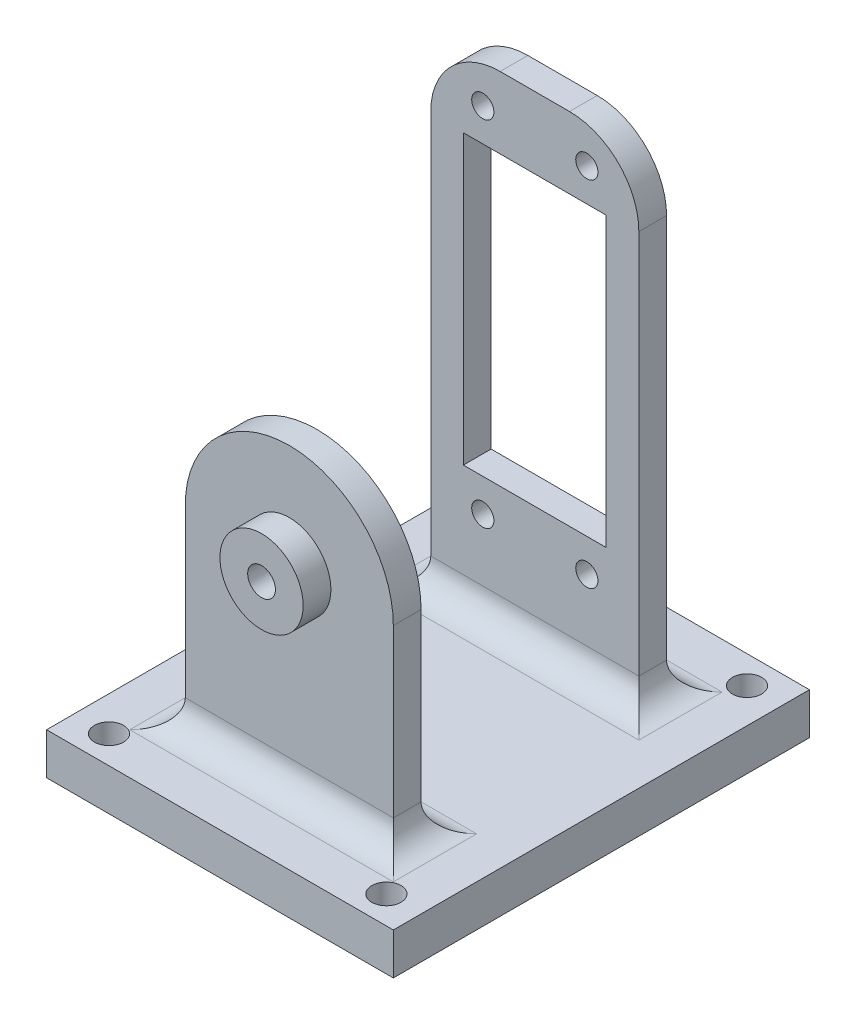
SolidWorks part; units mm, degrees
ref_plane "Front Plane" through (0, 0, 0) normal (0, 0, 1) x (1, 0, 0)
ref_plane "Top Plane" through (0, 0, 0) normal (0, 1, 0) x (1, 0, 0)
ref_plane "Right Plane" through (0, 0, 0) normal (1, 0, 0) x (0, 0, -1)
sketch "Sketch1" plane through (0, 0, 0) normal (0, 0, 1) x (1, 0, 0)
  line L0 (0, 0) -> (0, 53.2406) construction
  line L5 (-15, -28) -> (15, -28)
  line L6 (-15, -28) -> (-15, 31.5)
  line L7 (-5, 41.5) -> (5, 41.5)
  line L8 (15, -28) -> (15, 31.5)
  line L10 (-10.3, -10.3) -> (10.3, -10.3)
  line L11 (-10.3, -10.3) -> (-10.3, 31.2)
  line L12 (-10.3, 31.2) -> (10.3, 31.2)
  line L13 (10.3, -10.3) -> (10.3, 31.2)
  arc A0 (5, 41.5) -> (15, 31.5) centre (5, 31.5) cw
  arc A1 (-15, 31.5) -> (-5, 41.5) centre (-5, 31.5) cw
  circle A2 centre (-7.5, 35.95) radius 1.6
  circle A3 centre (-7.5, -15.05) radius 1.6
  circle A4 centre (7.5, 35.95) radius 1.6
  circle A5 centre (7.5, -15.05) radius 1.6
  dimension "D4" = 10
  dimension "D10" = 3.2
  dimension "D13" = 3.2
  dimension "D1" = 30
  dimension "D2" = 41.5
  dimension "D3" = 28
  dimension "D5" = 20.6
  dimension "D6" = 31.2
  dimension "D7" = 10.3
  dimension "D8" = 7.5
  dimension "D9" = 35.95
  dimension "D11" = 7.5
  dimension "D12" = 15.05
extrude "Boss-Extrude1" add sketch "Sketch1" along normal blind 4
ref_plane "Plane1" through (0, 0, 39.4) normal (0, 0, 1) x (1, 0, 0)
sketch "Sketch2" plane through (0, 0, 39.4) normal (0, 0, 1) x (1, 0, 0)
  line L0 (0, 0) -> (0, 30.7043) construction
  line L1 (-15, -28) -> (15, -28)
  line L2 (-15, -28) -> (-15, 0)
  line L4 (15, -28) -> (15, 0)
  arc A0 (-15, 0) -> (15, 0) centre (0, 0) cw
  point P8 (0, 0)
  dimension "D3" = 15
  dimension "D1" = 30
  dimension "D2" = 28
extrude "Boss-Extrude2" add sketch "Sketch2" against normal blind 4 separate body
sketch "Sketch3" plane through (0, 0, 39.4) normal (0, 0, 1) x (1, 0, 0)
  circle A0 centre (0, 0) radius 6
  dimension "D1" = 12
extrude "Boss-Extrude3" add sketch "Sketch3" along normal blind 4
sketch "Sketch4" plane through (0, 0, 43.4) normal (0, 0, 1) x (1, 0, 0)
  circle A0 centre (0, 0) radius 2
  dimension "D1" = 4
extrude "Cut-Extrude1" cut sketch "Sketch4" against normal through all
ref_plane "Plane2" through (0, -28, 0) normal (0, 1, 0) x (1, 0, 0)
sketch "Sketch5" plane through (0, -28, 0) normal (0, 1, 0) x (1, 0, 0)
  line L0 (0, 0) -> (0, -51.9066) construction
  line L1 (-25, 10.6) -> (25, 10.6)
  line L2 (-25, 10.6) -> (-25, -49.4)
  line L3 (-25, -49.4) -> (25, -49.4)
  line L4 (25, 10.6) -> (25, -49.4)
  line L5 (-15, 0) -> (15, 0) construction
  line L7 (-16.5, -39.4) -> (16.5, -39.4) construction
  dimension "D2" = 10.6
  dimension "D1" = 50
  dimension "D3" = 10
  dimension "D4" = 60
extrude "Boss-Extrude4" add sketch "Sketch5" against normal blind 6
sketch "Sketch6" plane through (0, -34, 0) normal (0, -1, 0) x (1, 0, 0)
  line L0 (-25, 19.4) -> (25, 19.4) construction
  line L1 (-25, -10.6) -> (-25, 49.4) construction
  line L2 (25, 49.4) -> (25, -10.6) construction
  line L3 (0, 49.4) -> (0, -10.6) construction
  line L4 (-25, 49.4) -> (25, 49.4) construction
  line L5 (25, -10.6) -> (-25, -10.6) construction
  circle A0 centre (-20, 45.4) radius 2.1
  circle A1 centre (20, 45.4) radius 2.1
  circle A2 centre (20, -6.6) radius 2.1
  circle A3 centre (-20, -6.6) radius 2.1
  dimension "D1" = 4.2
  dimension "D2" = 20
  dimension "D3" = 45.4
extrude "Cut-Extrude2" cut sketch "Sketch6" against normal up to surface (6 mm away) up to face at (0, -28, 2)
fillet "Fillet1" radius 4 8 edges at (0, -28, 39.4) (-15, -28, 37.4) (15, -28, 37.4) (0, -28, 35.4) (15, -28, 2) (0, -28, 4) (-15, -28, 2) (0, -28, 0)
equation "\"L1\"= 120mm'Upper arm"
equation "\"L3\"= 75mm'Wrist→TCP"
equation "\"h0\"= 75mm'Shoulder height"
equation "\"t_link\"= 3mm'Link plate thickness"
equation "\"t_bracket\"= 4mm'Bracket thickness"
equation "\"d_pin\"= 4mm'Pin diameter (M4)"
equation "\"c_fit\"= 0.2mm'Nominal clearance - measured PLA 2026-10-01"
equation "\"L2\"= 120mm'Forearm"
equation "\"c_fit_pivot\"= \"c_fit\" + 0.05mm'Gripper pivot clearance - chosen 0.25 mm 2026-10-01"
equation "\"d_pin_gripper\"= 3mm'Gripper pivot diameter"
equation "\"w_link\"= 20mm'Link plate depth (bending direction)"
equation "\"w_gap\"= 20mm'Twin-plate gap - provisional, set by elbow servo mount"
equation "\"d_boss\"= 13mm'MG996R output boss dia - from downloaded model, verify with calipers"
equation "\"c_boss\"= 1mm'Radial clearance around servo boss"
equation "\"d_servo_hole\"= \"d_boss\" + 2 * \"c_boss\"'Plate clearance hole for servo boss (15 mm)"
equation "\"t_rim\"= 9.5mm'Min material around servo hole (M3 hole + 3 mm webs each side)"
equation "\"w_link_end\"= \"d_servo_hole\" + 2 * \"t_rim\"'Link plate end width at servo end (34 mm)"
equation "\"d_hole_m3\"= \"d_pin_gripper\" + \"c_fit\"'M3 bolt clearance hole (spacer and adapter bolts)"
equation "\"d_hole_pivot\"= \"d_pin\" + \"c_fit_pivot\"'M4 pivot hole where the pin rotates (4.25 mm)"
equation "\"d_horn\"= 20mm'Horn disc diameter (circular horn) - from MG996R model"
equation "\"t_horn\"= 2.3mm'Horn disc thickness"
equation "\"g_horn\"= 2.2mm'Gap from horn disc to plate 2 inner face - from MockShoulder"
equation "\"d_horn_pocket\"= \"d_horn\" + \"c_fit\"'Adapter pocket for horn disc (20.2 mm)"
equation "\"h_horn_pocket\"= \"g_horn\" + \"t_horn\"'Pocket depth from adapter plate-2 face (4.5 mm)"
equation "\"d_horn_screw_cb\"= 8.5mm'Recess for horn centre-screw head (head is 7.5 mm)"
equation "\"h_horn_screw_cb\"= 2.6mm'Recess depth (head is 2.35 mm tall)"
equation "\"d_adapter\"= 26mm'Horn adapter outer diameter"
equation "\"h_adapter\"= \"w_gap\"'Adapter length, fills the plate gap"
equation "\"t_adapter_floor\"= 2mm'Floor under horn disc that the horn screws pass through"
equation "\"d_horn_screw_hole\"= 2.2mm'Clearance for M2 self-tapper through the floor"
equation "\"r_horn_screw\"= 7mm'Horn screw hole radius (14 mm square pattern)"
equation "\"d_access\"= 4mm'Access bore for the M2 screws from the plate-1 side"
equation "\"d_insert_m3\"= 4.2mm'Hole for M3 heat-set insert - check the insert maker spec"
equation "\"h_insert_m3\"= 6mm'Insert hole depth"
equation "\"x_adapter_bolt\"= 6mm'Adapter bolt offset from pin, along the arm toward its middle"
equation "\"y_adapter_bolt\"= 5mm'Adapter bolt offset from pin, across the arm (+/-)"
equation "\"d_csk_m3\"= 6.4mm'Countersink diameter in plate 1 for M3 flat head (90 deg)"
equation "\"h_pin_bore\"= 10mm'M4 pin engagement depth in the adapter"
equation "\"c_win\"= 0.3mm'Servo window clearance per side in bracket wall A - starting value, tune after a test print"
equation "\"l_servo\"= 40.9mm'MG996R case length without ears - from the model"
equation "\"w_servo\"= 20mm'MG996R case width - from the model"
equation "\"r_servo_short\"= 10mm'Shaft axis to the short end of the case - from the model"
equation "\"r_servo_long\"= \"l_servo\" - \"r_servo_short\"'Shaft axis to the long end of the case (30.9 mm)"
equation "\"l_ear_holes\"= 51mm'MG996R ear hole spacing along the case - from the model"
equation "\"w_ear_holes\"= 15mm'MG996R ear hole spacing across the case - from the model"
equation "\"a_ear\"= 8.4mm'Servo ear seating face to plate-2 outer face - from MockShoulder"
equation "\"l_window\"= \"l_servo\" + 2 * \"c_win\"'Wall A window length (41.5 mm)"
equation "\"w_window\"= \"w_servo\" + 2 * \"c_win\"'Wall A window width (20.6 mm)"
equation "\"g_wall_a\"= \"a_ear\" - \"t_bracket\"'Gap behind wall A to plate 2 (4.4 mm) - ear screw heads sit here"
equation "\"g_wall_b\"= 1mm'Plate 1 outer face to wall B - thrust washer"
equation "\"d_axis_turret\"= 34mm'Shoulder axis to turret mounting face - PLACEHOLDER until the turret is designed"
equation "\"t_foot\"= 6mm'Bracket foot thickness"
equation "\"h_wall_top\"= 41.5mm'Wall A top above the shoulder axis (long-end ear holes + 4 mm)"
equation "\"w_wall\"= 30mm'Bracket wall A and B width"
equation "\"w_foot\"= 50mm'Bracket foot width across the walls"
equation "\"t_boss_b\"= 4mm'Extra thickness of the pin boss on the outside of wall B"
equation "\"d_boss_b\"= 12mm'Pin boss diameter on wall B"
equation "\"D1@Sketch1\"=\"w_wall\""
equation "\"D2@Sketch1\"=\"h_wall_top\""
equation "\"D3@Sketch1\"=\"d_axis_turret\" - \"t_foot\""
equation "\"D5@Sketch1\"=\"w_window\""
equation "\"D6@Sketch1\"=\"r_servo_long\" + \"c_win\""
equation "\"D7@Sketch1\"=\"r_servo_short\" + \"c_win\""
equation "\"D8@Sketch1\"=\"w_ear_holes\"/2"
equation "\"D9@Sketch1\"=\"l_ear_holes\"/2 + \"l_servo\"/2 - \"r_servo_short\""
equation "\"D10@Sketch1\"=\"d_hole_m3\""
equation "\"D11@Sketch1\"=\"w_ear_holes\"/2"
equation "\"D12@Sketch1\"=\"l_ear_holes\"/2 - (\"l_servo\"/2 - \"r_servo_short\")"
equation "\"D13@Sketch1\"=\"d_hole_m3\""
equation "\"D1@Boss-Extrude1\"=\"t_bracket\""
equation "\"D1@Sketch3\"=\"d_boss_b\""
equation "\"D1@Boss-Extrude3\"=\"t_boss_b\""
equation "\"D1@Sketch4\"=\"d_pin\""
equation "\"D1@Sketch5\"=\"w_foot\""
equation "\"D1@Boss-Extrude4\"=\"t_foot\""
equation "\"D1@Sketch6\"=\"d_insert_m3\""
